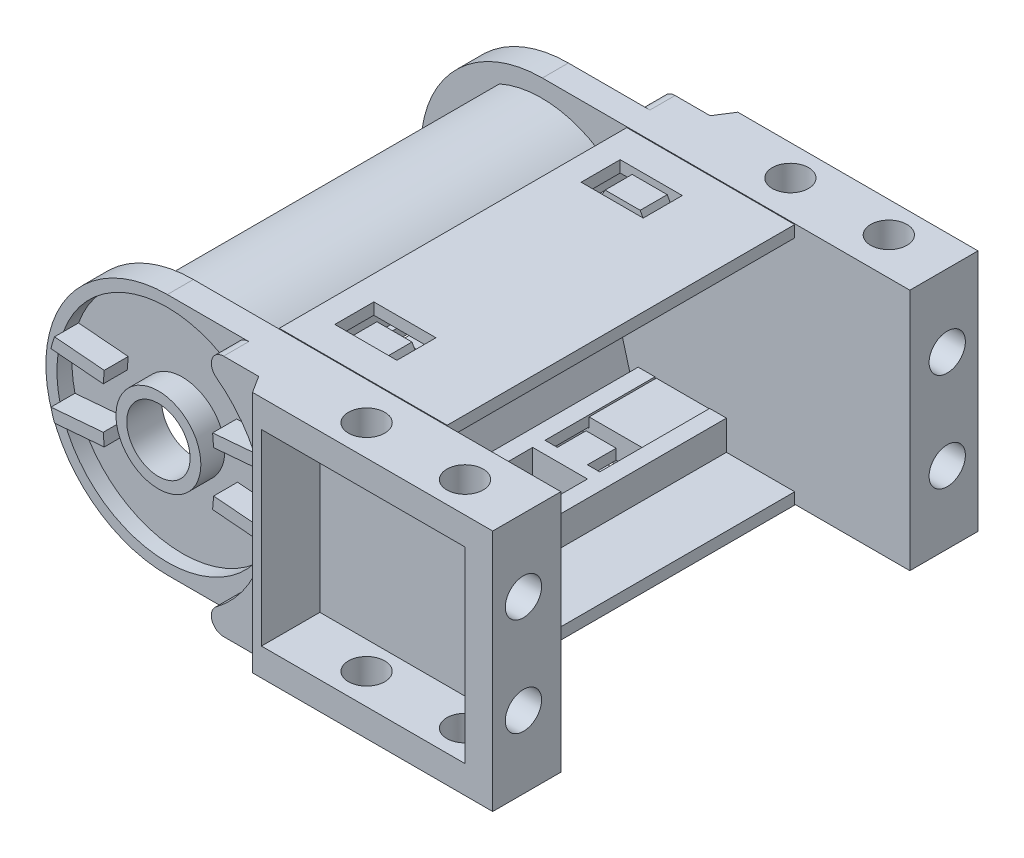
SolidWorks part; units mm, degrees
material "ABS"
ref_plane "Front Plane" through (0, 0, 0) normal (0, 0, 1) x (1, 0, 0)
ref_plane "Top Plane" through (0, 0, 0) normal (0, 1, 0) x (1, 0, 0)
ref_plane "Right Plane" through (0, 0, 0) normal (1, 0, 0) x (0, 0, -1)
sketch "Sketch1" plane through (0, 0, 0) normal (0, 0, 1) x (1, 0, 0)
  line L0 (0, 19.75) -> (59.75, 19.75)
  line L1 (59.75, 19.75) -> (59.75, -19.75)
  line L2 (59.75, -19.75) -> (0, -19.75)
  arc A0 (0, 19.75) -> (0, -19.75) centre (0, 0) ccw
  point P1 (-19.75, 0)
  dimension "D1" = 39.5
  dimension "D2" = 79.5
extrude "Boss-Extrude1" add sketch "Sketch1" against normal blind 11.08 from offset 39.45
sketch "Sketch2" plane through (0, 0, 39.45) normal (0, 0, 1) x (1, 0, 0)
  line L0 (59.75, -19.75) -> (59.75, 19.75) construction
  line L1 (22.15, 15.25) -> (55.25, 15.25)
  line L2 (22.15, 15.25) -> (22.15, -15.25)
  line L3 (22.15, -15.25) -> (55.25, -15.25)
  line L4 (55.25, 15.25) -> (55.25, -15.25)
  line L5 (38.7, -15.25) -> (38.7, 15.25) construction
  line L6 (22.15, 0) -> (55.25, 0) construction
  line L7 (59.75, 19.75) -> (0, 19.75) construction
  point P0 (38.7, 0)
  dimension "D1" = 4.5
  dimension "D2" = 4.5
  dimension "D3" = 33.1
extrude "Cut-Extrude1" cut sketch "Sketch2" against normal blind 9.5
sketch "Sketch3" plane through (0, 0, 39.45) normal (0, 0, 1) x (1, 0, 0)
  line L0 (0, -19.75) -> (59.75, -19.75) construction
  line L1 (59.75, 19.75) -> (0, 19.75) construction
  line L2 (0, -19.75) -> (18.95, -19.75)
  line L3 (18.95, 19.75) -> (0, 19.75)
  line L4 (18.95, 19.75) -> (18.95, -19.75)
  line L5 (59.75, -19.75) -> (59.75, 19.75) construction
  arc A0 (0, 19.75) -> (0, -19.75) centre (0, 0) ccw construction
  arc A1 (0, 19.75) -> (0, -19.75) centre (0, 0) ccw
  point P7 (-19.75, 0)
  dimension "D1" = 40.8
extrude "Cut-Extrude2" cut sketch "Sketch3" against normal blind 2.75
chamfer "Chamfer1" distance 1.75 distance2 2.75 1 edges at (18.95, 0, 39.45) first distance on face at (39.35, 0, 39.45)
sketch "Sketch20" plane through (0, 0, 36.7) normal (0, 0, 1) x (1, 0, 0)
  circle A0 centre (0, 0) radius 20.15
  dimension "D1" = 40.3
extrude "Cut-Extrude10" cut sketch "Sketch20" against normal blind 4.1
fillet "Fillet3" radius 2 2 edges at (3.995, -19.75, 34.65) (3.995, 19.75, 34.65)
sketch "Sketch21" plane through (0, 0, 32.6) normal (0, 0, 1) x (1, 0, 0)
  circle A0 centre (0, 0) radius 17.95
  dimension "D1" = 35.9
extrude "Cut-Extrude11" cut sketch "Sketch21" against normal offset from surface (2.45 mm away) 6.55 up to face at (15.6464, 15.8587, 36.7)
sketch "Sketch22" plane through (0, 0, 30.15) normal (0, 0, 1) x (1, 0, 0)
  circle A0 centre (0, 0) radius 5.15
  dimension "D1" = 10.3
extrude "Cut-Extrude12" cut sketch "Sketch22" against normal through all
sketch "Sketch23" plane through (0, 0, 30.15) normal (0, 0, 1) x (1, 0, 0)
  line L0 (17.2108, 5.0982) -> (8.8897, 4.4035) construction
  line L1 (-17.95, 0) -> (17.95, 0) construction
  line L2 (16.8907, 6.075) -> (8.8065, 5.4)
  line L3 (17.4716, 4.1165) -> (8.9729, 3.4069)
  line L4 (8.8065, 5.4) -> (8.9729, 3.4069)
  line L5 (17.1276, 6.0948) -> (8.8065, 5.4) construction
  line L6 (17.4716, -4.1165) -> (8.9729, -3.4069)
  line L7 (8.8065, -5.4) -> (8.9729, -3.4069)
  line L8 (16.8907, -6.075) -> (8.8065, -5.4)
  line L9 (17.294, 4.1017) -> (8.9729, 3.4069) construction
  line L10 (0, 0) -> (0, -5.15) construction
  line L11 (-8.8065, -5.4) -> (-8.9729, -3.4069)
  line L12 (-16.8907, -6.075) -> (-8.8065, -5.4)
  line L13 (-17.4716, -4.1165) -> (-8.9729, -3.4069)
  line L14 (-17.4716, 4.1165) -> (-8.9729, 3.4069)
  line L15 (-8.8065, 5.4) -> (-8.9729, 3.4069)
  line L16 (-16.8907, 6.075) -> (-8.8065, 5.4)
  circle A0 centre (0, 0) radius 5.15 construction
  circle A1 centre (0, 0) radius 5.15
  circle A2 centre (0, 0) radius 6.9
  circle A3 centre (0, 0) radius 17.95 construction
  arc A5 (17.4716, 4.1165) -> (16.8907, 6.075) centre (0, 0) ccw
  arc A6 (17.4716, -4.1165) -> (16.8907, -6.075) centre (0, 0) cw
  arc A7 (-17.4716, -4.1165) -> (-16.8907, -6.075) centre (0, 0) ccw
  arc A8 (-17.4716, 4.1165) -> (-16.8907, 6.075) centre (0, 0) cw
  point P12 (0, 0)
  dimension "D1" = 13.8
  dimension "D4" = 8.35
  dimension "D5" = 10.8
  dimension "D6" = 12.15
  dimension "D2" = 1
  dimension "D3" = 1
extrude "Boss-Extrude11" add sketch "Sketch23" along normal blind 3.9
sketch "Sketch6" plane through (0, 19.75, 0) normal (0, 1, 0) x (1, 0, 0)
  line L0 (59.75, -34.45) -> (20.7, -34.45) construction
  line L1 (59.75, -28.37) -> (59.75, -39.45) construction
  line L3 (59.75, -39.45) -> (20.7, -39.45) construction
  circle A0 centre (50.25, -34.45) radius 2.95
  circle A1 centre (34.25, -34.45) radius 2.95
  dimension "D1" = 5.9
  dimension "D2" = 16
  dimension "D3" = 9.5
  dimension "D4" = 5
extrude "Cut-Extrude4" cut sketch "Sketch6" against normal through all
sketch "Sketch7" plane through (59.75, 0, 0) normal (1, 0, 0) x (0, 0, -1)
  line L0 (-34.45, 19.75) -> (-34.45, -19.75) construction
  line L1 (-28.37, 19.75) -> (-39.45, 19.75) construction
  line L2 (-28.37, -19.75) -> (-39.45, -19.75) construction
  line L3 (-34.45, 0) -> (-28.37, 0) construction
  line L4 (-28.37, -19.75) -> (-28.37, 19.75) construction
  line L5 (-39.45, -19.75) -> (-39.45, 19.75) construction
  circle A0 centre (-34.45, 8) radius 2.95
  circle A1 centre (-34.45, -8) radius 2.95
  dimension "D1" = 16
  dimension "D2" = 5.9
  dimension "D3" = 5
extrude "Cut-Extrude5" cut sketch "Sketch7" against normal up to next
sketch "Sketch12" plane through (0, 0, 28.37) normal (0, 0, -1) x (-1, 0, 0)
  line L0 (-27.425, 17.15) -> (-18.325, 17.15)
  line L1 (-22.875, 17.15) -> (-22.875, 13.25) construction
  line L2 (-27.425, 17.15) -> (-28.25, 15.65)
  line L3 (-28.25, 14.85) -> (-27.225, 14.85)
  line L4 (-27.225, 14.85) -> (-27.225, 13.25)
  line L5 (-18.525, 14.85) -> (-18.525, 13.25)
  line L6 (-17.5, 14.85) -> (-18.525, 14.85)
  line L7 (-18.325, 17.15) -> (-17.5, 15.65)
  line L8 (-18.525, 13.25) -> (-27.225, 13.25)
  line L9 (-28.25, 15.65) -> (-28.25, 14.85)
  line L10 (0, 0) -> (-59.75, 0) construction
  line L11 (-59.75, -19.75) -> (-59.75, 19.75) construction
  line L20 (-17.5, 15.65) -> (-17.5, 14.85)
  line L21 (-22.875, -17.15) -> (-22.875, -13.25) construction
  line L22 (-17.5, -15.65) -> (-17.5, -14.85)
  line L23 (-28.25, -15.65) -> (-28.25, -14.85)
  line L24 (-18.525, -13.25) -> (-27.225, -13.25)
  line L25 (-18.325, -17.15) -> (-17.5, -15.65)
  line L26 (-17.5, -14.85) -> (-18.525, -14.85)
  line L27 (-18.525, -14.85) -> (-18.525, -13.25)
  line L28 (-27.225, -14.85) -> (-27.225, -13.25)
  line L29 (-28.25, -14.85) -> (-27.225, -14.85)
  line L30 (-27.425, -17.15) -> (-28.25, -15.65)
  line L31 (-27.425, -17.15) -> (-18.325, -17.15)
  point P3 (-22.875, 17.15)
  dimension "D1" = 10.75
  dimension "D2" = 31.5
  dimension "D3" = 26.5
  dimension "D4" = 34.3
  dimension "D5" = 8.7
  dimension "D6" = 2.3
  dimension "D7" = 0.8
  dimension "D8" = 9.1
extrude "Boss-Extrude4" add sketch "Sketch12" along normal offset from surface (10.92 mm away) 22 up to face at (40.225, 0, 39.45)
sketch "Sketch13" plane through (0, 0, 17.45) normal (0, 0, -1) x (-1, 0, 0)
  line L0 (-26.7, 17.15) -> (-25.725, 18.9)
  line L1 (-18.325, 17.15) -> (-27.425, 17.15) construction
  line L2 (-25.725, 18.9) -> (-20.025, 18.9)
  line L3 (-20.025, 18.9) -> (-19.05, 17.15)
  line L4 (-26.7, 17.15) -> (-19.05, 17.15)
  line L5 (-22.875, 18.9) -> (-22.875, 17.15) construction
  line L6 (0, 0) -> (-59.75, 0) construction
  line L7 (-59.75, -19.75) -> (-59.75, 19.75) construction
  line L8 (-20.025, -18.9) -> (-19.05, -17.15)
  line L9 (-26.7, -17.15) -> (-19.05, -17.15)
  line L10 (-26.7, -17.15) -> (-25.725, -18.9)
  line L11 (-25.725, -18.9) -> (-20.025, -18.9)
  point P8 (-22.875, 17.15)
  dimension "D1" = 7.65
  dimension "D2" = 5.7
  dimension "D3" = 1.75
extrude "Boss-Extrude5" add sketch "Sketch13" against normal blind 4.4 from offset 1.1 offset against normal yes
sketch "Sketch14" plane through (0, 0, 0) normal (0, 0, 1) x (1, 0, 0)
  line L0 (41.15, 19.75) -> (13.85, 19.75)
  line L1 (59.75, 19.75) -> (0, 19.75) construction
  line L2 (13.85, 19.75) -> (11.7872, 12.25)
  line L3 (59.75, -19.75) -> (59.75, 19.75) construction
  line L4 (41.15, 17.87) -> (30.05, 17.87)
  line L5 (15.2827, 17.87) -> (12.6469, 8.2867)
  line L6 (-6.85, 15.5588) -> (-6.0925, 13.8382)
  line L7 (41.15, 19.75) -> (41.15, 17.87)
  line L8 (30.05, 13.05) -> (30.05, 17.87)
  line L9 (27.325, 13.05) -> (30.05, 13.05)
  line L10 (27.325, 13.05) -> (27.325, 14.75)
  line L11 (27.325, 14.75) -> (28.35, 14.75)
  line L12 (28.35, 14.75) -> (28.35, 17.87)
  line L13 (28.35, 17.87) -> (17.4, 17.87)
  line L14 (41.15, 17.87) -> (15.2827, 17.87) construction
  line L15 (18.425, 13.05) -> (15.7, 13.05)
  line L16 (15.7, 13.05) -> (15.7, 17.87)
  line L17 (22.875, 13.25) -> (22.875, 19.75) construction
  line L18 (18.425, 13.25) -> (18.425, 14.75)
  line L19 (17.4, 14.75) -> (17.4, 15.65)
  line L20 (18.425, 14.75) -> (17.4, 14.75)
  line L21 (18.425, 13.05) -> (18.425, 14.75)
  line L22 (17.4, 14.75) -> (17.4, 17.87)
  line L23 (18.425, 14.75) -> (17.4, 14.75)
  line L24 (18.525, 13.25) -> (27.225, 13.25) construction
  line L25 (15.7, 17.87) -> (15.2827, 17.87)
  arc A0 (11.7872, 12.25) -> (-6.85, 15.5588) centre (0, 0) ccw
  arc A1 (12.6469, 8.2867) -> (-6.0925, 13.8382) centre (0, 0) ccw
  dimension "D1" = 17
  dimension "D2" = 48
  dimension "D3" = 27.3
  dimension "D4" = 7.5
  dimension "D5" = 18.6
  dimension "D7" = 0.1
  dimension "D6" = 1.88
  dimension "D8" = 1.7
extrude "Boss-Extrude6" add sketch "Sketch14" along normal mid plane 56.5 separate body
sketch "Sketch15" plane through (0, 19.75, 0) normal (0, 1, 0) x (1, 0, 0)
  line L1 (27.925, -16.85) -> (17.825, -16.85)
  line L2 (27.925, -16.85) -> (27.925, -23.2)
  line L5 (27.925, -23.2) -> (17.825, -23.2)
  line L6 (17.825, -16.85) -> (17.825, -23.2)
  line L7 (22.875, -23.2) -> (22.875, -16.85) construction
  line L8 (27.925, -20.025) -> (17.825, -20.025) construction
  line L9 (0, 0) -> (44.1536, 0) construction
  line L10 (17.825, 16.85) -> (17.825, 23.2)
  line L11 (27.925, 23.2) -> (17.825, 23.2)
  line L12 (27.925, 16.85) -> (27.925, 23.2)
  line L13 (27.925, 16.85) -> (17.825, 16.85)
  line L14 (19.05, -18.55) -> (26.7, -22.95) construction
  point P14 (22.875, -20.75)
  point P172 (22.875, -20.025)
  dimension "D1" = 10.1
  dimension "D2" = 33.7
  dimension "D3" = 46.4
extrude "Cut-Extrude9" cut sketch "Sketch15" against normal up to surface (5 mm away) up to face at (27.8375, 14.75, 0)
sketch "Sketch16" plane through (0, 13.05, 0) normal (0, -1, 0) x (1, 0, 0)
  line L0 (30.05, 28.25) -> (30.05, -28.25) construction
  line L1 (30.05, 10.375) -> (15.7, 10.375)
  line L2 (30.05, 10.375) -> (30.05, -10.375)
  line L3 (30.05, -10.375) -> (15.7, -10.375)
  line L4 (15.7, 10.375) -> (15.7, -10.375)
  line L5 (22.875, -10.375) -> (22.875, 10.375) construction
  line L6 (30.05, 0) -> (15.7, 0) construction
  line L7 (15.7, 28.25) -> (15.7, -28.25) construction
  line L8 (18.425, 28.25) -> (18.425, -28.25) construction
  line L9 (27.325, -8.375) -> (18.425, -8.375)
  line L10 (27.325, -8.375) -> (27.325, 8.375)
  line L11 (27.325, 8.375) -> (18.425, 8.375)
  line L12 (18.425, -8.375) -> (18.425, 8.375)
  line L13 (22.875, 8.375) -> (22.875, -8.375) construction
  line L14 (27.325, 0) -> (18.425, 0) construction
  point P10 (22.875, 0)
  point P212 (22.875, 0)
  dimension "D1" = 20.75
  dimension "D2" = 2
extrude "Boss-Extrude7" add sketch "Sketch16" against normal up to surface (4.82 mm away) up to face at (35.6, 17.87, 0)
sketch "Sketch17" plane through (0, 13.05, 0) normal (0, -1, 0) x (1, 0, 0)
  line L0 (22.875, 10.375) -> (22.875, -10.375) construction
  line L1 (28.35, 10.375) -> (17.4, 10.375) construction
  line L2 (18.425, -10.375) -> (27.325, -10.375) construction
  line L3 (25.325, 10.375) -> (25.325, 15.05)
  line L4 (20.425, 10.375) -> (20.425, 15.05)
  line L5 (20.425, 15.05) -> (25.325, 15.05)
  line L6 (22.875, 0) -> (41.15, 0) construction
  line L7 (41.15, 28.25) -> (41.15, -28.25) construction
  line L8 (25.325, 10.375) -> (20.425, 10.375)
  line L9 (20.425, -10.375) -> (20.425, -15.05)
  line L10 (20.425, -15.05) -> (25.325, -15.05)
  line L11 (25.325, -10.375) -> (25.325, -15.05)
  line L12 (25.325, -10.375) -> (20.425, -10.375)
  dimension "D1" = 4.9
  dimension "D2" = 30.1
extrude "Boss-Extrude8" add sketch "Sketch17" against normal up to surface (1.7 mm away) up to face at (17.9125, 14.75, 19.3125)
mirror "Mirror1" about plane through (0, 0, 0) normal (0, 0, 1) of bodies 113 121
mirror "Mirror2" about plane through (0, 0, 0) normal (0, 1, 0) of bodies 119 115
sketch "Sketch24" plane through (0, 19.75, 0) normal (0, 1, 0) x (1, 0, 0)
  line L0 (41.15, 28.25) -> (13.85, 28.25) construction
  line L1 (41.15, -28.25) -> (35.35, -28.25)
  line L2 (41.15, -28.25) -> (41.15, 28.25)
  line L3 (41.15, 28.25) -> (35.35, 28.25)
  line L4 (35.35, -28.25) -> (35.35, 28.25)
  line L5 (38.25, 28.25) -> (38.25, -28.25) construction
  line L6 (41.15, 0) -> (35.35, 0) construction
  point P148 (38.25, 0)
  dimension "D1" = 5.8
extrude "Cut-Extrude13" [suppressed] cut sketch "Sketch24" against normal up to next
